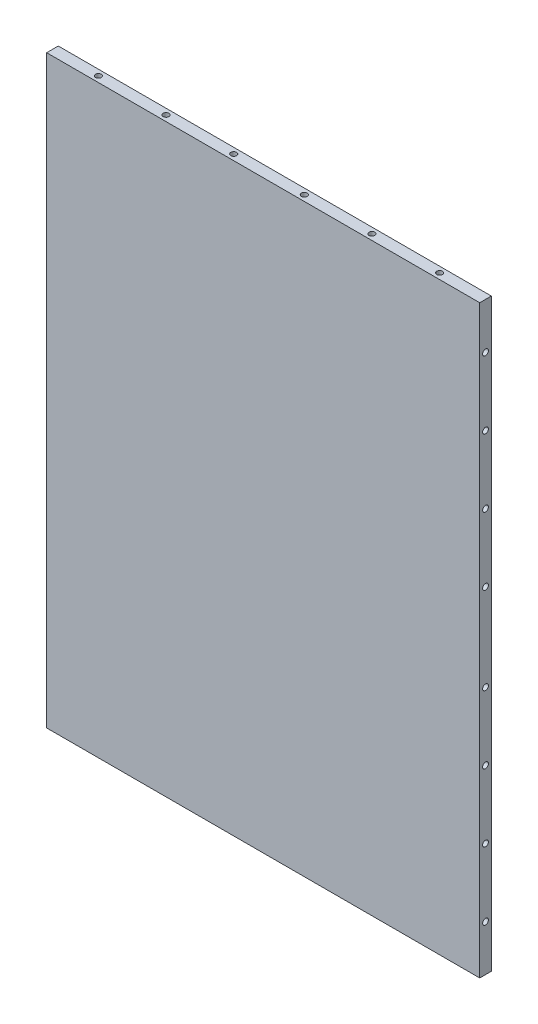
SolidWorks part; units mm, degrees
ref_plane "Alzado" through (0, 0, 0) normal (0, 0, 1) x (1, 0, 0)
ref_plane "Planta" through (0, 0, 0) normal (0, 1, 0) x (1, 0, 0)
ref_plane "Vista lateral" through (0, 0, 0) normal (1, 0, 0) x (0, 0, -1)
sketch "Croquis1" plane through (0, 0, 0) normal (0, 0, 1) x (1, 0, 0)
  line L1 (224, 302.5) -> (-224, 302.5)
  line L2 (224, 302.5) -> (224, -302.5)
  line L3 (224, -302.5) -> (-224, -302.5)
  line L4 (-224, 302.5) -> (-224, -302.5)
  dimension "D1" = 448
  dimension "D2" = 605
  dimension "D3" = 224
  dimension "D4" = 302.5
extrude "Saliente-Extruir2" add sketch "Croquis1" along normal mid plane 12
sketch "Croquis3" plane through (0, 0, 0) normal (1, 0, 0) x (0, 0, -1)
  line L0 (-6, 302.5) -> (6, 302.5) construction
  line L1 (-37.0183, 0) -> (52.3914, 0) construction
  circle A0 centre (0, 255) radius 3
  circle A1 centre (0, 185) radius 3
  circle A2 centre (0, 115) radius 3
  circle A3 centre (0, 45) radius 3
  circle A4 centre (0, -45) radius 3
  circle A5 centre (0, -115) radius 3
  circle A6 centre (0, -185) radius 3
  circle A7 centre (0, -255) radius 3
  dimension "D1" = 47.5
  dimension "D2" = 4
extrude "Cortar-Extruir2" cut sketch "Croquis3" against normal blind 27 from offset 225
mirror "Simetría1" about plane through (0, 0, 0) normal (1, 0, 0) of "Cortar-Extruir2"
sketch "Croquis4" plane through (0, 0, 0) normal (0, 1, 0) x (1, 0, 0)
  line L0 (-224, -6) -> (-224, 6) construction
  line L1 (0, 6) -> (0, -6) construction
  line L2 (224, 6) -> (-224, 6) construction
  line L3 (224, -6) -> (-224, -6) construction
  circle A0 centre (-176.5, 0) radius 3
  circle A1 centre (-106.5, 0) radius 3
  circle A2 centre (-36.5, 0) radius 3
  circle A3 centre (36.5, 0) radius 3
  circle A4 centre (106.5, 0) radius 3
  circle A5 centre (176.5, 0) radius 3
  dimension "D1" = 47.5
  dimension "D2" = 3
extrude "Cortar-Extruir3" cut sketch "Croquis4" against normal blind 22 from offset 303
mirror "Simetría2" about plane through (0, 0, 0) normal (0, 1, 0) of "Cortar-Extruir3"
